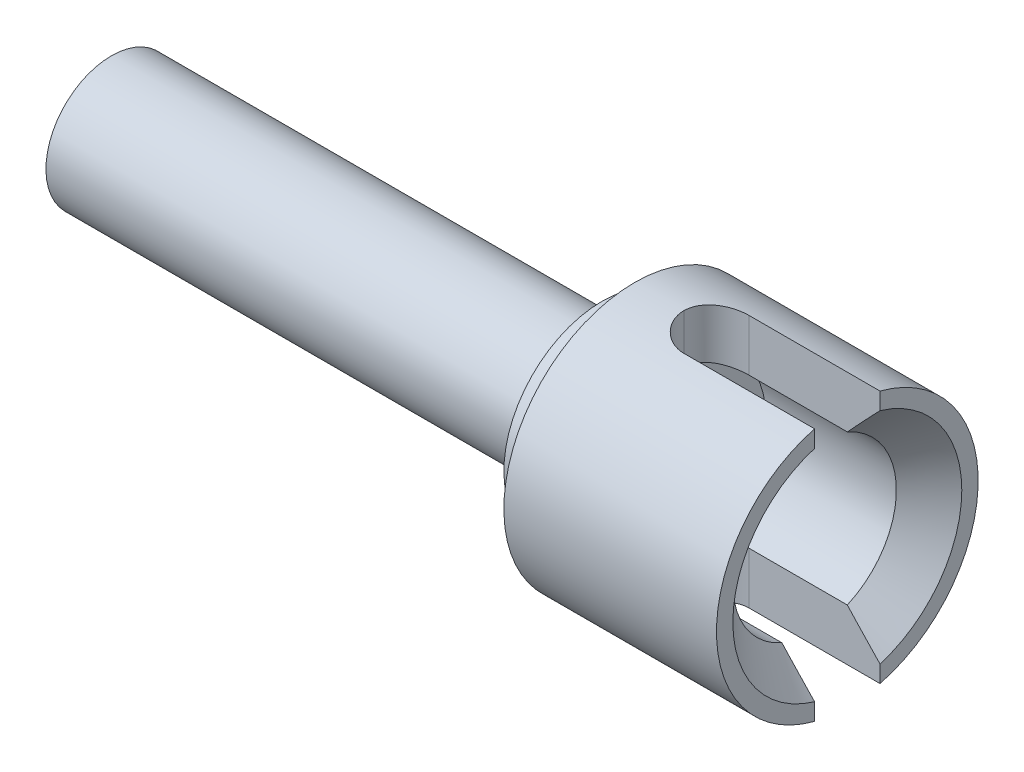
SolidWorks part; units mm, degrees
ref_plane "Front" through (0, 0, 0) normal (0, 0, 1) x (1, 0, 0)
ref_plane "Top" through (0, 0, 0) normal (0, 1, 0) x (1, 0, 0)
ref_plane "Right" through (0, 0, 0) normal (1, 0, 0) x (0, 0, -1)
sketch "Sketch1" plane through (0, 0, 0) normal (0, 0, 1) x (1, 0, 0)
  line L1 (0, 0) -> (-25.4, 0)
  line L2 (0, 0) -> (0, 3.175)
  line L3 (0, 3.175) -> (-25.4, 3.175)
  line L4 (-25.4, 0) -> (-25.4, 3.175)
  line L5 (0, 0) -> (2.3813, 0)
  line L6 (0, 0) -> (0, 6.35)
  line L7 (0, 6.35) -> (2.3813, 6.35)
  line L8 (2.3813, 0) -> (2.3813, 6.35)
  line L9 (2.3813, 6.35) -> (10.3187, 6.35)
  line L10 (2.3813, 6.35) -> (2.3813, 3.9688)
  line L11 (2.3813, 3.9688) -> (10.3187, 3.9688)
  line L12 (10.3187, 6.35) -> (10.3187, 3.9688)
  line L13 (0, 3.175) -> (-1.5875, 3.175)
  line L14 (0, 3.175) -> (0, 4.7625)
  line L15 (0, 4.7625) -> (-1.5875, 4.7625)
  line L16 (-1.5875, 3.175) -> (-1.5875, 4.7625)
  point P11 (6.35, 3.9688)
  dimension "D1" = 3.175
  dimension "D2" = 25.4
  dimension "D3" = 6.35
  dimension "D4" = 2.3813
  dimension "D5" = 2.3813
  dimension "D6" = 4.7625
  dimension "D7" = 1.5875
  dimension "D8" = 7.9375
revolve "Revolve1" add sketch "Sketch1" angle 360 about L1 region at (-12.7, 1.5875, 0) region at (1.1906, 3.175, 0) region at (-0.7938, 3.9688, 0) region at (6.35, 5.1594, 0)
sketch "Sketch2" plane through (0, 0, 0) normal (0, 1, 0) x (1, 0, 0)
  line L0 (10.3187, -3.9688) -> (10.3187, 3.9688) construction
  line L1 (2.3813, -3.9688) -> (2.3813, 3.9688) construction
  line L2 (10.3187, -3.9688) -> (10.3187, 3.9688)
  line L3 (2.3813, -3.9688) -> (2.3813, 3.9688)
  line L4 (2.3813, 3.9688) -> (10.3187, 3.9688)
  line L5 (3.175, 1.5875) -> (3.175, -1.5875)
  line L6 (2.3813, -1.5875) -> (10.3187, -1.5875)
  line L7 (2.3813, -1.5875) -> (2.3813, 1.5875)
  line L8 (2.3813, 1.5875) -> (10.3187, 1.5875)
  line L9 (10.3187, -1.5875) -> (10.3187, 1.5875)
  line L10 (2.3813, -1.5875) -> (10.3187, 1.5875) construction
  line L11 (2.3813, 1.5875) -> (10.3187, -1.5875) construction
  circle A0 centre (6.35, 0) radius 1.5875
  point P6 (6.35, 3.9688)
  dimension "D1" = 3.175
  dimension "D2" = 0.7937
extrude "Cut-Extrude1" cut sketch "Sketch2" against normal through all both and the other way through all contours L8 L3 L6 L5 | A0 L8 L5 L6 | A0 | A0 L6 L2 L8 region at (8.9347, 0, 0) region at (4.1716, 0, 0) region at (6.35, 0, 0) region at (2.7781, 0, 0)
fillet "Fillet1" radius 1.5875 4 edges at (2.3813, -4.8929, -1.5875) (2.3813, -4.8929, 1.5875) (2.3813, 4.8929, 1.5875) (2.3813, 4.8929, -1.5875)
chamfer "Chamfer1" distance 1.5875 angle 45 2 edges at (10.3187, 0, -3.9688) (10.3187, 0, 3.9688)
